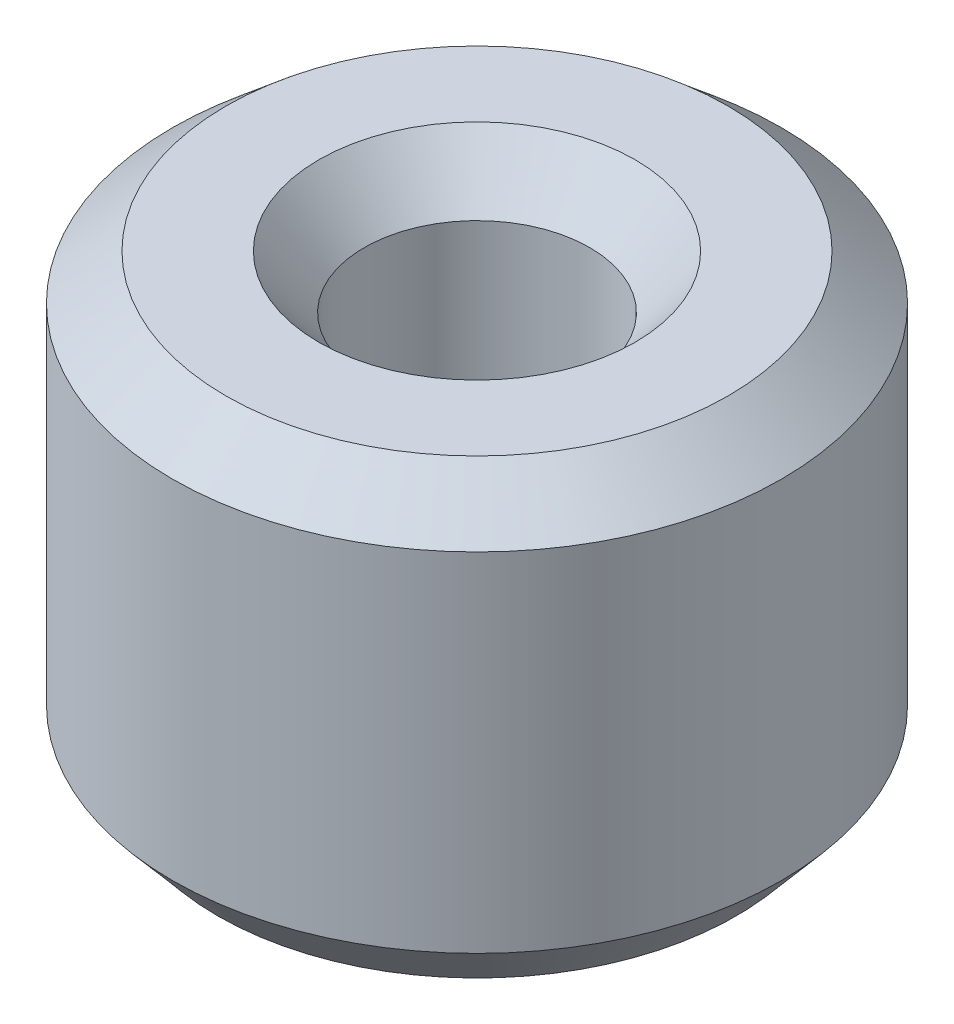
SolidWorks part; units mm, degrees
ref_plane "Front Plane" through (0, 0, 0) normal (0, 0, 1) x (1, 0, 0)
ref_plane "Top Plane" through (0, 0, 0) normal (0, 1, 0) x (1, 0, 0)
ref_plane "Right Plane" through (0, 0, 0) normal (1, 0, 0) x (0, 0, -1)
sketch "Sketch1" plane through (0, 0, 0) normal (0, 1, 0) x (1, 0, 0)
  circle A0 centre (0, 0) radius 12.5
  dimension "SLEEVE_OD" = 25
extrude "Boss-Extrude1" add sketch "Sketch1" along normal blind 18.3282
sketch "Sketch2" plane through (0, 0, 0) normal (0, 1, 0) x (1, 0, 0)
  circle A0 centre (0, 0) radius 4.6298
  dimension "BORE_D" = 9.2596
extrude "Cut-Extrude1" cut sketch "Sketch2" along normal through all
chamfer "Chamfer1" distance 1.8626 angle 49.647 4 edges at (0, 18.3282, 4.6298) (0, 0, 4.6298) (0, 0, 12.5) (0, 18.3282, 12.5) first distance on face at (0, 18.3282, 4.6298) first distance on face at (0, 0, 4.6298) first distance on face at (0, 18.3282, 12.5)
